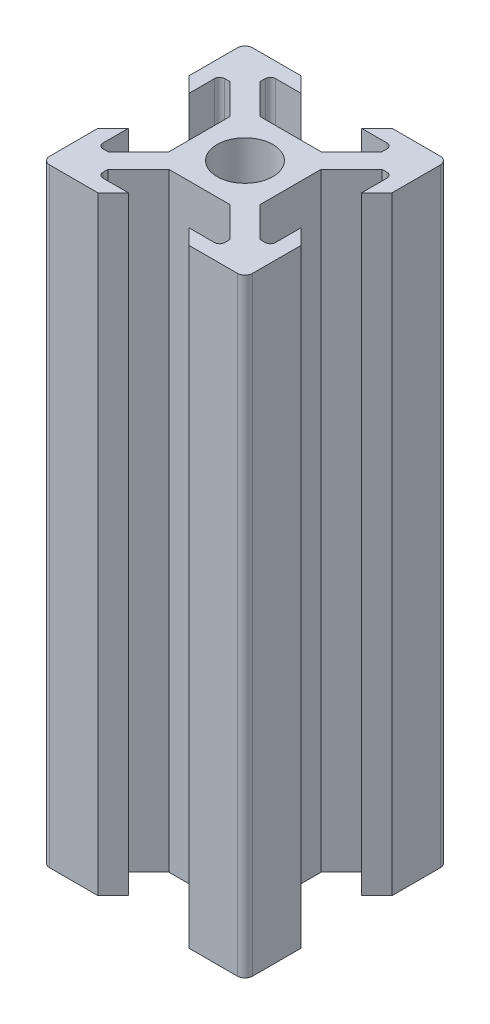
SolidWorks part; units mm, degrees
ref_plane "Front Plane" through (0, 0, 0) normal (0, 0, 1) x (1, 0, 0)
ref_plane "Top Plane" through (0, 0, 0) normal (0, 1, 0) x (1, 0, 0)
ref_plane "Right Plane" through (0, 0, 0) normal (1, 0, 0) x (0, 0, -1)
sketch "Sketch1" plane through (0, 0, 0) normal (0, 1, 0) x (1, 0, 0)
  line L0 (-4.5, 3) -> (-10, 3) construction
  line L1 (-10, 10) -> (10, 10) construction
  line L2 (-10, 10) -> (-10, -10) construction
  line L3 (-10, -10) -> (10, -10) construction
  line L4 (10, 10) -> (10, -10) construction
  line L5 (-10, 10) -> (10, -10) construction
  line L6 (-10, -10) -> (10, 10) construction
  line L7 (-3, 4.5) -> (3, 4.5)
  line L8 (-4.5, 3) -> (-4.5, -3)
  line L9 (-3, -4.5) -> (3, -4.5)
  line L10 (4.5, 3) -> (4.5, -3)
  line L11 (-4.5, 4.5) -> (4.5, -4.5) construction
  line L12 (-4.5, -4.5) -> (4.5, 4.5) construction
  line L13 (-10, 4.5) -> (-8.5, 3)
  line L14 (-8.5, 3) -> (-8.5, 6)
  line L15 (-4.5, 3) -> (-7.5, 6)
  line L16 (-7.5, 6) -> (-8.5, 6)
  line L17 (-10, 10) -> (-10, 4.5)
  line L18 (-3, 4.5) -> (-3, 10) construction
  line L19 (-10, 10) -> (-4.5, 10)
  line L20 (-6, 7.5) -> (-6, 8.5)
  line L21 (-3, 4.5) -> (-6, 7.5)
  line L22 (-3, 8.5) -> (-6, 8.5)
  line L23 (-4.5, 10) -> (-3, 8.5)
  line L24 (10, 10) -> (4.5, 10)
  line L25 (10, 10) -> (10, 4.5)
  line L26 (10, 4.5) -> (8.5, 3)
  line L27 (8.5, 3) -> (8.5, 6)
  line L28 (7.5, 6) -> (8.5, 6)
  line L29 (4.5, 3) -> (7.5, 6)
  line L30 (3, 4.5) -> (6, 7.5)
  line L31 (3, 8.5) -> (6, 8.5)
  line L32 (4.5, 10) -> (3, 8.5)
  line L33 (6, 7.5) -> (6, 8.5)
  line L34 (10, -10) -> (10, -4.5)
  line L35 (10, -10) -> (4.5, -10)
  line L36 (4.5, -10) -> (3, -8.5)
  line L37 (3, -8.5) -> (6, -8.5)
  line L38 (6, -7.5) -> (6, -8.5)
  line L39 (3, -4.5) -> (6, -7.5)
  line L40 (4.5, -3) -> (7.5, -6)
  line L41 (8.5, -3) -> (8.5, -6)
  line L42 (10, -4.5) -> (8.5, -3)
  line L43 (7.5, -6) -> (8.5, -6)
  line L44 (-10, -10) -> (-4.5, -10)
  line L45 (-10, -10) -> (-10, -4.5)
  line L46 (-10, -4.5) -> (-8.5, -3)
  line L47 (-8.5, -3) -> (-8.5, -6)
  line L48 (-7.5, -6) -> (-8.5, -6)
  line L49 (-4.5, -3) -> (-7.5, -6)
  line L50 (-3, -4.5) -> (-6, -7.5)
  line L51 (-3, -8.5) -> (-6, -8.5)
  line L52 (-4.5, -10) -> (-3, -8.5)
  line L53 (-6, -7.5) -> (-6, -8.5)
  circle A0 centre (0, 0) radius 2.75
  point P0 (0, 0)
  point P60 (0, 0)
  dimension "D1" = 5.5
  dimension "D2" = 4
  dimension "D3" = 45
extrude "Boss-Extrude2" add sketch "Sketch1" along normal blind 60 contours L19 L23 L22 L20 L21 L7 L30 L33 L31 L32 L24 L25 L26 L27 L28 L29 L10 L40 L43 L41 L42 L34 L35 L36 L37 L38 L39 L9 L50 L53 L51 L52 L44 L45 L46 L47 L48 L49 L8 L15 L16 L14 L13 L17
extrude "Cut-Extrude4" cut sketch "Sketch1<3>" along normal blind 80 contours A0
sketch "Sketch1<3>" plane through (0, 0, 0) normal (0, 1, 0) x (1, 0, 0) same geometry as "Sketch1"
fillet "Fillet7" radius 0.75 4 edges at (-10, 30, 10) (10, 30, 10) (10, 30, -10) (-10, 30, -10)
fillet "Fillet8" radius 0.5 8 edges at (-8.5, 30, -6) (-6, 30, -8.5) (8.5, 30, -6) (6, 30, -8.5) (8.5, 30, 6) (6, 30, 8.5) (-6, 30, 8.5) (-8.5, 30, 6)
